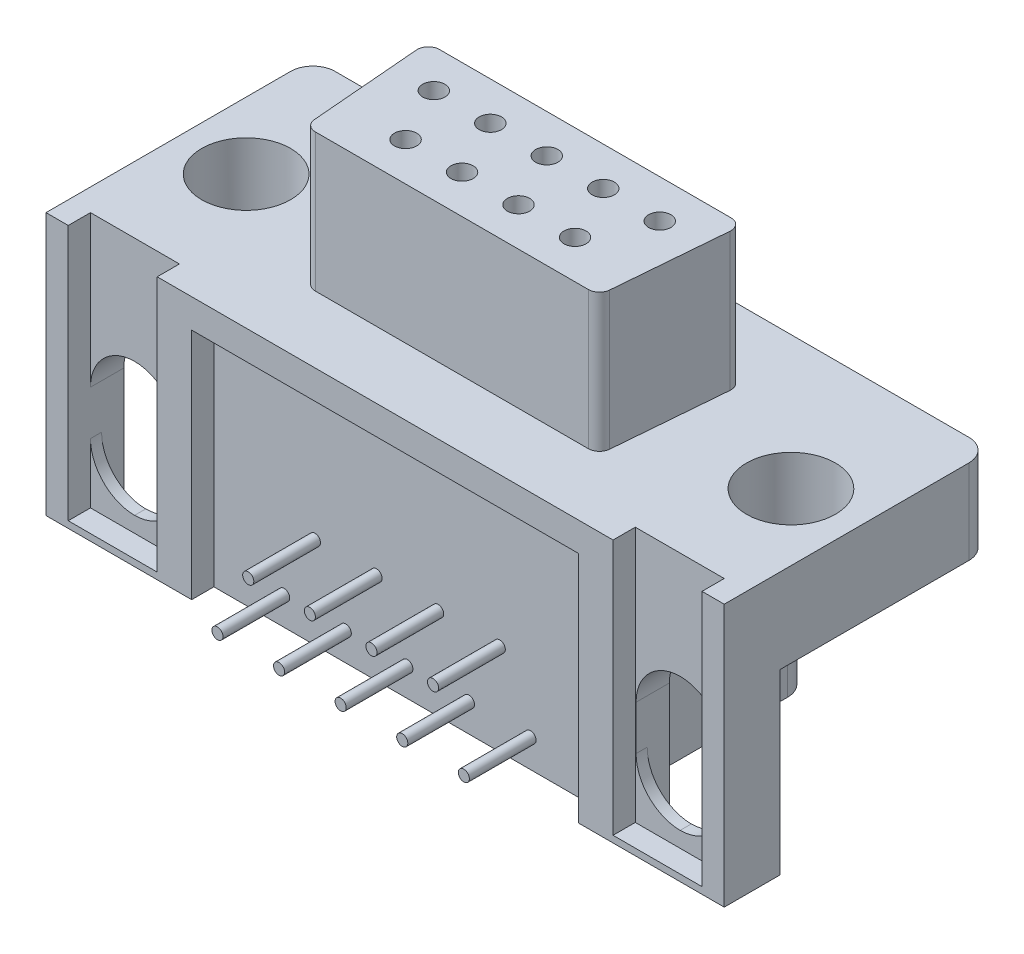
SolidWorks part; units mm, degrees
ref_plane "前视基准面" through (0, 0, 0) normal (0, 0, 1) x (1, 0, 0)
ref_plane "上视基准面" through (0, 0, 0) normal (0, 1, 0) x (1, 0, 0)
ref_plane "右视基准面" through (0, 0, 0) normal (1, 0, 0) x (0, 0, -1)
sketch "草图1" plane through (0, 0, 0) normal (0, 1, 0) x (1, 0, 0)
  line L0 (-1000, 0) -> (49000, 0) construction
  line L1 (0, -1000) -> (0, 49000) construction
  line L2 (-15.25, 6) -> (15.25, 6)
  line L3 (-15.25, 6) -> (-15.25, -6)
  line L4 (15.25, 6) -> (15.25, -6)
  line L5 (-15.25, -6) -> (15.25, -6)
  point P10 (0, 6)
  point P11 (15.25, 0)
  point P12 (-15.25, 0)
  dimension "D1" = 12
  dimension "D2" = 30.5
extrude "凸台-拉伸1" add sketch "草图1" along normal blind 18
sketch "草图2" plane through (0, 18, 0) normal (0, 1, 0) x (1, 0, 0)
  line L0 (0, -1000) -> (0, 49000) construction
  line L1 (-1000, 0) -> (49000, 0) construction
  line L2 (-6.5566, 3) -> (6.5566, 3)
  line L3 (-6.1399, -3) -> (6.1399, -3)
  line L4 (-7.0549, 2.4585) -> (-6.6382, -2.5415)
  line L5 (7.0549, 2.4585) -> (6.6382, -2.5415)
  line L6 (6.6, -3) -> (6.6191, -3.1069)
  line L7 (-15.25, 6) -> (-15.25, -6)
  line L8 (-15.25, -6) -> (15.25, -6)
  line L9 (15.25, -6) -> (15.25, 6)
  line L10 (15.25, 6) -> (-15.25, 6)
  arc A0 (-6.1399, -3) -> (-6.6382, -2.5415) centre (-6.1399, -2.5) cw
  arc A1 (7.0549, 2.4585) -> (6.5566, 3) centre (6.5566, 2.5) ccw
  arc A2 (-6.5566, 3) -> (-7.0549, 2.4585) centre (-6.5566, 2.5) ccw
  arc A3 (6.6382, -2.5415) -> (6.1399, -3) centre (6.1399, -2.5) cw
  point P8 (0, 3)
  point P15 (7.1, 3)
  point P18 (-7.1, 3)
  dimension "D3" = 0.5
  dimension "D4" = 0.5
  dimension "D1" = 6
  dimension "D2" = 14.2
extrude "切除-拉伸2" cut sketch "草图2" against normal blind 6.2 contours L7 L8 L9 L10 | L3 A3 L5 A1 L2 A2 L4 A0
sketch "草图3" plane through (0, 11.8, 0) normal (0, 1, 0) x (1, 0, 0)
  line L0 (15.25, -6) -> (15.25, 6) construction
  line L1 (10.25, -5) -> (10.25, -6)
  line L2 (-15.25, -6) -> (15.25, -6) construction
  line L3 (10.25, -6) -> (14.25, -6)
  line L4 (14.25, -6) -> (14.25, -5)
  line L5 (10.25, -5) -> (14.25, -5)
  line L6 (0, 0) -> (0, 6.2756) construction
  line L7 (-10.25, -5) -> (-14.25, -5)
  line L8 (-14.25, -6) -> (-14.25, -5)
  line L9 (-10.25, -6) -> (-14.25, -6)
  line L10 (-10.25, -5) -> (-10.25, -6)
  circle A0 centre (12.25, 0) radius 2
  circle A1 centre (-12.25, 0) radius 2
  dimension "D1" = 4
  dimension "D2" = 3
  dimension "D3" = 1
extrude "切除-拉伸3" cut sketch "草图3" against normal blind 11.5
sketch "草图4" plane through (0, 0, 0) normal (0, -1, 0) x (1, 0, 0)
  line L0 (0, 0) -> (0, -13.0768) construction
  line L1 (8.5, -4.6) -> (8.5, 3.5)
  line L2 (-8.5, -4.6) -> (-8.5, 3.5)
  line L3 (8.5, -4.6) -> (-8.5, -4.6)
  line L4 (15.25, -6) -> (-15.25, -6) construction
  line L5 (15.25, 3.5) -> (8.5, 3.5)
  line L6 (-15.25, 6) -> (15.25, 6) construction
  line L7 (-8.5, 3.5) -> (-15.25, 3.5)
  line L8 (15.25, 3.5) -> (15.25, -4.6)
  line L9 (15.25, 6) -> (15.25, -6) construction
  line L10 (15.25, -4.6) -> (15.25, -6)
  line L11 (15.25, -6) -> (-15.25, -6)
  line L12 (-15.25, -6) -> (-15.25, 3.5)
  dimension "D1" = 17
  dimension "D2" = 1.4
  dimension "D3" = 2.5
extrude "切除-拉伸4" cut sketch "草图4" against normal blind 8
sketch "草图5" plane through (0, 0, 0) normal (0, -1, 0) x (1, 0, 0)
  line L0 (0, -1000) -> (0, 49000) construction
  line L1 (-14.25, 4.5) -> (-10.2856, 4.5)
  line L2 (14.25, 3.5) -> (10.2856, 3.5)
  line L3 (-10.25, 6) -> (-14.25, 6)
  line L4 (14.25, 4.5) -> (10.2856, 4.5)
  line L5 (14.25, 4.5) -> (14.25, 3.5)
  line L6 (10.2856, 4.5) -> (10.2856, 3.5)
  line L8 (-14.25, 4.5) -> (-14.25, 3.5)
  line L9 (-8.5, 3.5) -> (-15.25, 3.5) construction
  line L10 (-14.25, 3.5) -> (-10.2856, 3.5)
  line L11 (-10.2856, 3.5) -> (-10.2856, 4.5)
  line M2 (8.5, 3.5) -> (15.25, 3.5)
  line M6 (-15.25, 3.5) -> (-8.5, 3.5)
  dimension "D1" = 1
extrude "切除-拉伸6" cut sketch "草图5" against normal blind 7 contours L4 L6 L5 M2 | L11 L1 L8 M6 region at (-12.2678, 0, 4) region at (12.2678, 0, 4)
sketch "草图6" plane through (0, 0, 4.5) normal (0, 0, -1) x (-1, 0, 0)
  line L0 (14.25, 1) -> (10.2856, 1)
  line L1 (14.25, 0) -> (15.25, 0) construction
  line L2 (10.2856, 7) -> (14.25, 7)
  line L3 (10.2856, 7) -> (10.2856, 1)
  line L4 (14.25, 7) -> (14.25, 1)
  line L5 (14.25, 7) -> (14.25, 0) construction
  dimension "D1" = 1
extrude "切除-拉伸7" cut sketch "草图6" against normal through all
fillet "圆角1" radius 2 4 edges at (-14.25, 1, 4.75) (-10.2856, 1, 4.75) (-14.25, 7, 4.25) (-10.2856, 7, 4.25)
mirror "镜向1" about plane through (0, 0, 0) normal (1, 0, 0) of "切除-拉伸7"
fillet "圆角2" radius 2 4 edges at (10.2856, 1, 4.75) (14.25, 1, 4.75) (10.2856, 7, 4.25) (14.25, 7, 4.25)
fillet "圆角3" radius 1 4 edges at (-15.25, 9.9, -6) (15.25, 9.9, -6) (-8.5, 4, -4.6) (8.5, 4, -4.6)
sketch "草图7" plane through (0, 0, 0) normal (0, -1, 0) x (1, 0, 0)
  line L0 (0, -1000) -> (0, 49000) construction
  line L1 (-8.7, 10.7507) -> (-8.7, 5)
  line L2 (-8.7, 5) -> (8.7, 5)
  line L3 (-15.25, 6) -> (15.25, 6) construction
  line L4 (-8.7, 10.7507) -> (8.7, 10.7507)
  line L5 (8.7, 10.7507) -> (8.7, 5)
  point P10 (0, 5)
  point P11 (0, 10.7507)
  dimension "D1" = 1
  dimension "D2" = 17.4
extrude "切除-拉伸8" cut sketch "草图7" against normal blind 10.5
sketch "草图8" plane through (0, 0, 5) normal (0, 0, 1) x (1, 0, 0)
  line L0 (-21.0537, 1.27) -> (18.738, 1.27) construction
  line L1 (-8.7, 0) -> (8.7, 0) construction
  line L2 (0, -1000) -> (0, 49000) construction
  circle A0 centre (0, 1.27) radius 0.25
  circle A1 centre (2.77, 1.27) radius 0.25
  circle A2 centre (5.54, 1.27) radius 0.25
  circle A3 centre (-5.54, 1.27) radius 0.25
  circle A4 centre (-2.77, 1.27) radius 0.25
  circle A5 centre (-1.385, 4.11) radius 0.25
  circle A6 centre (1.385, 4.11) radius 0.25
  circle A7 centre (-4.155, 4.11) radius 0.25
  circle A8 centre (4.155, 4.11) radius 0.25
  dimension "D2" = 0.5
  dimension "D4" = 0.5
  dimension "D5" = 2.84
  dimension "D6" = 2.77
  dimension "D8" = 2.77
  dimension "D7" = 2
  dimension "D1" = 1.27
  dimension "D3" = 3
sketch "草图9" plane through (0, 18, 0) normal (0, 1, 0) x (1, 0, 0)
  line L0 (-1000, 0) -> (49000, 0) construction
  line L1 (0, -1000) -> (0, 49000) construction
  circle A0 centre (0, 1.27) radius 0.5
  circle A2 centre (2.54, 1.27) radius 0.5
  circle A4 centre (5.08, 1.27) radius 0.5
  circle A7 centre (-5.08, 1.27) radius 0.5
  circle A9 centre (-2.54, 1.27) radius 0.5
  circle A11 centre (-1.27, -1.27) radius 0.5
  circle A13 centre (-3.81, -1.27) radius 0.5
  circle A18 centre (3.81, -1.27) radius 0.5
  circle A20 centre (1.27, -1.27) radius 0.5
  circle A22 centre (1.27, 1.27) radius 0.5 [skipped]
  circle A23 centre (3.81, 1.27) radius 0.5 [skipped]
  dimension "D1" = 1
  dimension "D2" = 1.27
  dimension "D3" = 5
extrude "切除-拉伸9" cut sketch "草图9" against normal blind 8
extrude "凸台-拉伸2" add sketch "草图8" along normal blind 3
